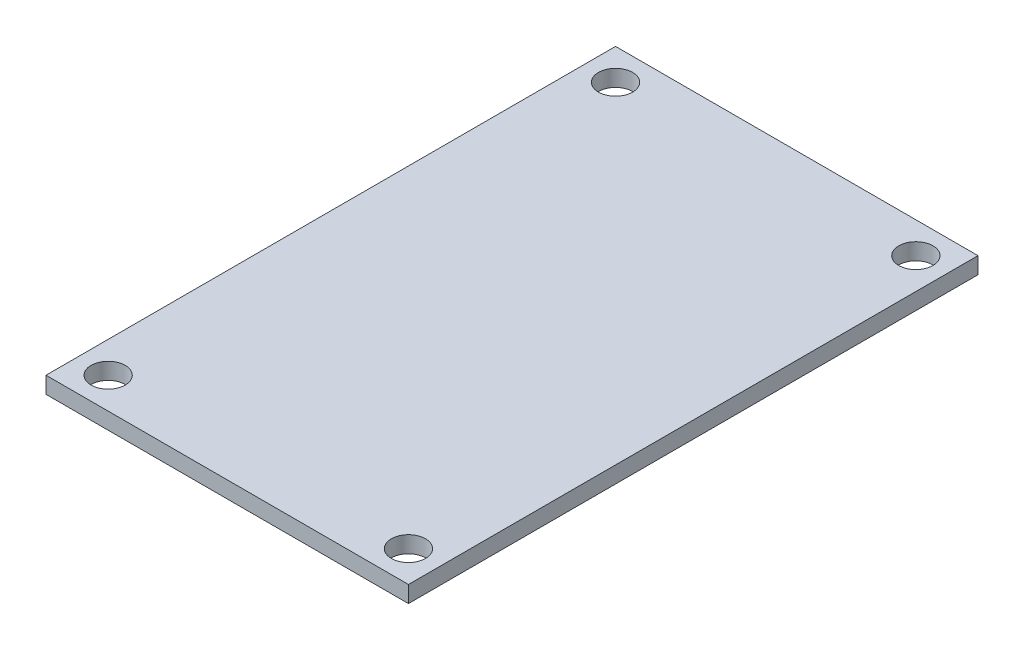
SolidWorks part; units mm, degrees
ref_plane "Front Plane" through (0, 0, 0) normal (0, 0, 1) x (1, 0, 0)
ref_plane "Top Plane" through (0, 0, 0) normal (0, 1, 0) x (1, 0, 0)
ref_plane "Right Plane" through (0, 0, 0) normal (1, 0, 0) x (0, 0, -1)
sketch "Sketch1" plane through (0, 0, 0) normal (0, 1, 0) x (1, 0, 0)
  line L0 (3, 52) -> (0, 52) construction
  line L1 (0, 0) -> (35, 0)
  line L2 (0, 0) -> (0, 55)
  line L3 (0, 55) -> (35, 55)
  line L4 (35, 0) -> (35, 55)
  line L5 (3, 52) -> (32, 52) construction
  line L6 (3, 52) -> (3, 3) construction
  line L7 (3, 3) -> (32, 3) construction
  line L8 (32, 52) -> (32, 3) construction
  line L9 (3, 52) -> (3, 55) construction
  line L10 (32, 3) -> (32, 0) construction
  line L11 (32, 3) -> (35, 3) construction
  circle A0 centre (3, 3) radius 1.65
  circle A1 centre (32, 3) radius 1.65
  circle A2 centre (3, 52) radius 1.65
  circle A3 centre (32, 52) radius 1.65
  dimension "D1" = 3.3
  dimension "D2" = 35
  dimension "D3" = 55
  dimension "D4" = 3
extrude "Boss-Extrude1" add sketch "Sketch1" along normal blind 1.6
